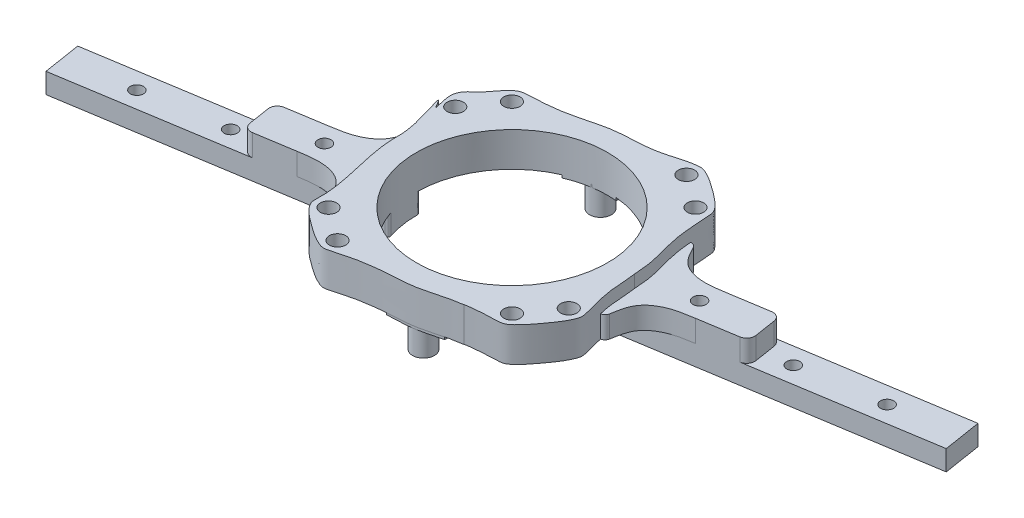
SolidWorks part; units mm, degrees
ref_plane "前视基准面" through (0, 0, 0) normal (0, 0, 1) x (1, 0, 0)
ref_plane "上视基准面" through (0, 0, 0) normal (0, 1, 0) x (1, 0, 0)
ref_plane "右视基准面" through (0, 0, 0) normal (1, 0, 0) x (0, 0, -1)
sketch "草图1" plane through (0, 0, 0) normal (0, 1, 0) x (1, 0, 0)
  circle A0 centre (0, 0) radius 17.5
  circle A1 centre (0, 0) radius 18.901
  dimension "D1" = 35
extrude "凸台-拉伸1" add sketch "草图1" along normal blind 2
sketch "草图2" plane through (0, 0, 0) normal (0, -1, 0) x (1, 0, 0)
  circle A0 centre (-10.7739, 21.1656) radius 1.5
  circle A1 centre (16.8004, 16.7872) radius 1.5
  circle A2 centre (21.1656, 10.7739) radius 1.5
  circle A3 centre (16.7872, -16.8004) radius 1.5
  circle A4 centre (10.7739, -21.1656) radius 1.5
  circle A5 centre (-16.8004, -16.7872) radius 1.5
  circle A6 centre (-21.1656, -10.7739) radius 1.5
  circle A7 centre (-16.7872, 16.8004) radius 1.5
  circle A28 centre (0, 0) radius 17.5
  spline S3 degree 3 poles (11.007, 19.7796) (11.3114, 19.6784) (14.2307, 19.3249) (16.1426, 19.3879) (17.8124, 19.1708) (19.4344, 17.903) (21.2548, 15.4236) (23.0457, 12.9332) (23.7495, 10.9887) (23.274, 8.5261) (21.9734, 4.7628) (22.0269, 1.1873) (21.7447, -0.683) knots 0 0 0 0 0.101498 0.202996 0.236379 0.269761 0.41266 0.555558 0.58894 0.622323 0.811161 1 1 1 1
  spline S4 degree 3 poles (21.7447, -0.683) (21.6101, -1.5752) (21.6055, -3.3542) (20.6884, -6.8809) (19.4904, -11.3054) (19.4855, -15.3122) (19.178, -17.8032) (17.9056, -19.4334) (15.4365, -21.2528) (12.9718, -22.9922) (11.1783, -23.6905) (8.6855, -23.5473) (4.924, -21.9674) (0.2192, -21.8124) (-3.3386, -21.5662) (-6.4463, -20.811) (-9.0785, -20.0903) (-12.7412, -19.4848) (-15.1253, -19.3752) (-17.5836, -19.2474) (-19.4002, -18.127) (-20.9244, -15.1209) (-24.3676, -13.3124) (-22.2966, -7.7817) (-24.7387, -12.2711) (-21.435, -3.3276) (-22.0126, 0.3206) (-20.5515, 8.1406) (-19.1109, 13.0019) (-19.2816, 16.8284) knots 0 0 0 0 0.02817 0.053916 0.112305 0.168269 0.178162 0.188055 0.230405 0.272754 0.280796 0.288838 0.34856 0.404524 0.432694 0.45844 0.502911 0.516855 0.572819 0.576577 0.592462 0.634812 0.677161 0.707499 0.719914 0.775878 0.831843 0.888071 1 1 1 1
  spline S5 degree 3 poles (-19.2816, 16.8284) (-19.323, 17.5174) (-18.1907, 19.2578) (-15.4061, 21.2421) (-12.9273, 23.0421) (-10.9838, 23.7431) (-9.3566, 23.4387) (-7.2233, 22.7077) (-4.4614, 22.2162) (-1.8337, 21.8607) (0.7732, 21.7432) (3.3794, 21.5754) (7.3403, 20.5662) (8.6858, 20.19) (9.8558, 19.9936) (10.7406, 19.8682) (11.007, 19.7796) knots 0 0 0 0 0.047987 0.150696 0.253406 0.277399 0.301393 0.374345 0.447298 0.510152 0.573007 0.641327 0.709648 0.853023 0.882058 1 1 1 1
  dimension "D1" = 3
extrude "凸台-拉伸2" add sketch "草图2" along normal blind 4.3 and the other way blind 2
sketch "草图3" plane through (0, -4.3, 0) normal (0, -1, 0) x (1, 0, 0)
  line L0 (8.2748, 9.3176) -> (-43.6533, 17.5632) construction
  line L1 (3.0581, 19.2587) -> (0, 0) construction
  line L2 (0, 0) -> (-3.0579, -19.2577) construction
  line L3 (-8.3782, -9.3002) -> (43.5499, -17.5457) construction
  circle A0 centre (3.0581, 19.2587) radius 2
  circle A1 centre (3.0581, 19.2587) radius 9 construction
  circle A2 centre (-3.0579, -19.2577) radius 2
  circle A3 centre (-3.0579, -19.2577) radius 9 construction
  dimension "D1" = 18
  dimension "D2" = 4
  dimension "D3" = 18
  dimension "D4" = 4
extrude "凸台-拉伸3" add sketch "草图3" along normal blind 5
sketch "草图5" plane through (0, -4.3, 0) normal (0, -1, 0) x (1, 0, 0)
  line L0 (0, 0) -> (38.9853, -6.1904) construction
  line L1 (70.6703, -14.0546) -> (-71.5479, 8.5279) construction
  circle A0 centre (3.0581, 19.2587) radius 5 construction
  arc A1 (-1.5944, 17.4272) -> (6.9144, 16.0761) centre (0, 0) cw
  arc A2 (-2.6852, -17.2928) -> (2.7444, 17.2835) centre (0, 0) ccw construction
  arc A3 (-1.3158, 21.6815) -> (-1.5944, 17.4272) centre (3.0581, 19.2587) ccw
  arc A4 (7.9454, 20.3141) -> (6.9144, 16.0761) centre (3.0581, 19.2587) cw
  arc A5 (-7.9672, -20.2075) -> (-6.9144, -16.0761) centre (-3.0581, -19.2587) cw
  arc A6 (-6.9144, -16.0761) -> (1.5944, -17.4272) centre (0, 0) ccw
  arc A7 (1.262, -21.7761) -> (1.5944, -17.4272) centre (-3.0581, -19.2587) ccw
  spline S0 degree 3 poles (-1.3158, 21.6815) (-0.2135, 21.5939) (1.3807, 21.5885) (3.4585, 21.3907) (5.444, 20.9684) (6.9168, 20.5202) (7.9454, 20.3141) knots 0 0 0 0 0.352817 0.508743 0.665414 1 1 1 1
  spline S2 degree 3 poles (-7.9672, -20.2075) (-6.892, -20.4656) (-5.3746, -20.9543) (-3.3377, -21.4099) (-1.319, -21.6234) (0.2201, -21.6535) (1.262, -21.7761) knots 0 0 0 0 0.352817 0.508743 0.665414 1 1 1 1
  dimension "D1" = 10
extrude "凸台-拉伸5" add sketch "草图5" along normal blind 0.5
sketch "草图6" plane through (0, -4.3, 0) normal (0, -1, 0) x (1, 0, 0)
  line L0 (0, 0) -> (83.2876, -13.2251) construction
  line L1 (70.6703, -14.0546) -> (-71.5479, 8.5279) construction
  line L2 (0, 0) -> (7.0837, 44.6111) construction
  line L3 (22.6545, 6.4264) -> (16.7134, 7.3698)
  line L4 (32.0065, -1.5404) -> (39.048, -2.6585)
  line L5 (71.6577, -7.8366) -> (-70.5606, 14.746) construction
  line L6 (-30.9094, 8.4499) -> (-37.9509, 9.5679)
  line L7 (40.2942, -4.3752) -> (39.9809, -6.3485)
  line L8 (19.5496, -13.1279) -> (13.6084, -12.1845)
  line L9 (30.9094, -8.4499) -> (37.9509, -9.5679)
  line L10 (39.6675, -8.3217) -> (39.9809, -6.3485)
  line L11 (-39.6675, 8.3217) -> (-39.9809, 6.3485)
  line L12 (-40.2942, 4.3752) -> (-39.9809, 6.3485)
  line L13 (-32.0065, 1.5404) -> (-39.048, 2.6585)
  line L14 (-19.5496, 13.1279) -> (-13.6084, 12.1845)
  line L15 (-22.6545, -6.4264) -> (-16.7134, -7.3698)
  circle A0 centre (21.1656, 10.7739) radius 2.5 construction
  arc A1 (1.5944, -17.4272) -> (6.9144, 16.0761) centre (0, 0) ccw construction
  arc A2 (13.3066, -11.3659) -> (16.1729, 6.685) centre (0, 0) ccw
  arc A3 (23.4842, 5.6027) -> (22.6545, 6.4264) centre (22.4977, 5.4388) ccw
  arc A4 (16.7134, 7.3698) -> (16.1729, 6.685) centre (16.6349, 6.876) ccw
  arc A5 (39.048, -2.6585) -> (40.2942, -4.3752) centre (38.8128, -4.14) cw
  arc A6 (13.6084, -12.1845) -> (13.3066, -11.3659) centre (13.6868, -11.6907) cw
  arc A7 (20.5935, -12.6017) -> (19.5496, -13.1279) centre (19.7064, -12.1402) cw
  arc A8 (37.9509, -9.5679) -> (39.6675, -8.3217) centre (38.1861, -8.0865) ccw
  arc A9 (-37.9509, 9.5679) -> (-39.6675, 8.3217) centre (-38.1861, 8.0865) ccw
  arc A10 (-39.048, 2.6585) -> (-40.2942, 4.3752) centre (-38.8128, 4.14) cw
  arc A11 (-20.5935, 12.6017) -> (-19.5496, 13.1279) centre (-19.7064, 12.1402) cw
  arc A12 (-13.6084, 12.1845) -> (-13.3066, 11.3659) centre (-13.6868, 11.6907) cw
  arc A13 (-16.1729, -6.685) -> (-13.3066, 11.3659) centre (0, 0) cw
  arc A14 (-16.7134, -7.3698) -> (-16.1729, -6.685) centre (-16.6349, -6.876) ccw
  arc A15 (-23.4842, -5.6027) -> (-22.6545, -6.4264) centre (-22.6575, -5.5997) ccw
  spline S0 degree 3 poles (20.5935, -12.6017) (20.8165, -12.1731) (21.4171, -11.0059) (22.8603, -8.9685) (26.5188, -7.7575) (29.1956, -8.1777) (30.9094, -8.4499) knots 0.057026 0.057026 0.057026 0.057026 0.169435 0.36028 0.616457 1 1 1 1
  spline S1 degree 3 poles (23.4842, 5.6027) (23.5634, 5.1261) (23.7729, 3.8302) (24.514, 1.446) (27.6174, -0.8387) (30.2927, -1.2683) (32.0065, -1.5404) knots 0.057026 0.057026 0.057026 0.057026 0.169435 0.36028 0.616457 1 1 1 1
  spline S2 degree 3 poles (-23.4842, -5.6027) (-23.5634, -5.1261) (-23.7729, -3.8302) (-24.514, -1.446) (-27.6174, 0.8387) (-30.2927, 1.2683) (-32.0065, 1.5404) knots 0.057026 0.057026 0.057026 0.057026 0.169435 0.36028 0.616457 1 1 1 1
  spline S3 degree 3 poles (-20.5935, 12.6017) (-20.8165, 12.1731) (-21.4171, 11.0059) (-22.8603, 8.9685) (-26.5188, 7.7575) (-29.1956, 8.1777) (-30.9094, 8.4499) knots 0.057026 0.057026 0.057026 0.057026 0.169435 0.36028 0.616457 1 1 1 1
  point P34 (15.8047, 7.514)
  dimension "D1" = 5
  dimension "D2" = 1
  dimension "D3" = 0.5
  dimension "D4" = 1.5
extrude "凸台-拉伸6" add sketch "草图6" against normal blind 4 separate body
sketch "草图7" plane through (0, -4.3, 0) normal (0, -1, 0) x (1, 0, 0)
  line L0 (17.2287, -6.2775) -> (70.5606, -14.746)
  line L1 (17.2287, -6.2775) -> (18.3258, 0.6319) construction
  line L2 (70.5606, -14.746) -> (71.6577, -7.8366)
  line L3 (18.3258, 0.6319) -> (71.6577, -7.8366)
  line L4 (17.2287, -6.2775) -> (71.6577, -7.8366) construction
  line L5 (70.5606, -14.746) -> (18.3258, 0.6319) construction
  line L6 (71.6577, -7.8366) -> (-70.5606, 14.746) construction
  line L7 (71.6266, -8.0321) -> (70.5916, -14.5504) construction
  line L8 (18.3258, 0.6319) -> (18.0775, 0.6713)
  line L9 (17.2287, -6.2775) -> (16.9804, -6.2381)
  line L10 (70.5606, -14.746) -> (-71.6577, 7.8366) construction
  line L11 (0, 0) -> (5.947, 37.4527) construction
  line L12 (-71.6577, 7.8366) -> (-70.5606, 14.746)
  line L13 (-17.2287, 6.2775) -> (-70.5606, 14.746)
  line L14 (-18.3258, -0.6319) -> (-71.6577, 7.8366)
  line L15 (-18.3258, -0.6319) -> (-18.0775, -0.6713)
  line L16 (-17.2287, 6.2775) -> (-16.9804, 6.2381)
  arc A0 (1.5944, -17.4272) -> (6.9144, 16.0761) centre (0, 0) ccw construction
  arc A1 (17.4991, 0.1726) -> (16.585, -5.5847) centre (0, 0) cw
  arc A2 (16.9804, -6.2381) -> (16.585, -5.5847) centre (17.0588, -5.7443) cw
  arc A3 (18.0775, 0.6713) -> (17.4991, 0.1726) centre (17.9991, 0.1775) ccw
  arc A4 (-18.0775, -0.6713) -> (-17.4991, -0.1726) centre (-17.9991, -0.1775) ccw
  arc A5 (-16.9804, 6.2381) -> (-16.585, 5.5847) centre (-17.0588, 5.7443) cw
  arc A6 (-16.585, 5.5847) -> (-17.4991, -0.1726) centre (0, 0) ccw
  point P1 (44.4432, -7.057)
  point P20 (16.3861, -6.1437)
  point P23 (17.4832, 0.7657)
  dimension "D1" = 0.5
extrude "凸台-拉伸7" add sketch "草图7" along normal up to surface (3.7 mm away)
sketch "草图8" plane through (0, -8, 0) normal (0, -1, 0) x (1, 0, 0)
  circle A0 centre (59.2576, -9.4094) radius 1.2
  circle A1 centre (44.4432, -7.057) radius 1.2
  circle A2 centre (29.6288, -4.7047) radius 1.2
  circle A3 centre (-29.6288, 4.7047) radius 1.2
  circle A4 centre (-44.4432, 7.057) radius 1.2
  circle A5 centre (-59.2576, 9.4094) radius 1.2
  dimension "D1" = 2.4
extrude "切除-拉伸1" cut sketch "草图8" against normal through all
